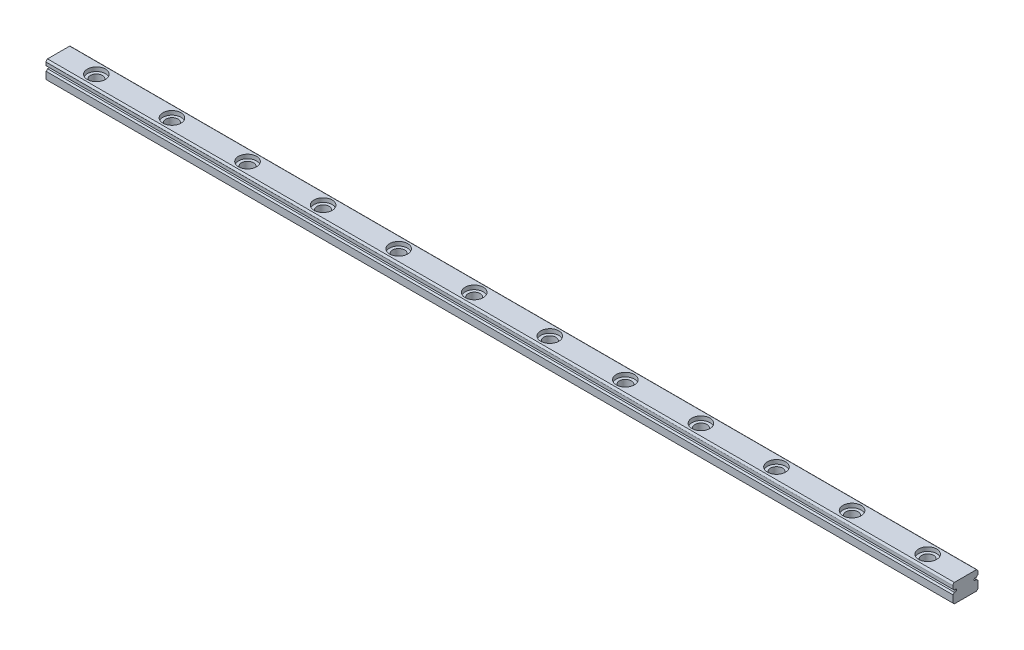
SolidWorks part; units mm, degrees
ref_plane "Front Plane" through (0, 0, 0) normal (0, 0, 1) x (1, 0, 0)
ref_plane "Top Plane" through (0, 0, 0) normal (0, 1, 0) x (1, 0, 0)
ref_plane "Right Plane" through (0, 0, 0) normal (1, 0, 0) x (0, 0, -1)
sketch "Sketch1" plane through (0, 0, 0) normal (1, 0, 0) x (0, 0, -1)
  line L0 (-2.5, 0.3) -> (-2.2, 0)
  line L1 (-2.2, 0) -> (2.2, 0)
  line L2 (2.2, 0) -> (2.5, 0.3)
  line L3 (2.5, 0.3) -> (2.5, 1.723)
  line L4 (2.1917, 2) -> (1.85, 2)
  line L5 (1.75, 2.1) -> (1.75, 2.3)
  line L6 (1.85, 2.4) -> (2.1917, 2.4)
  line L7 (2.5, 2.677) -> (2.5, 3.3)
  line L8 (2.2, 3.7) -> (-2.2, 3.7)
  line L9 (-2.5, 3.3) -> (-2.5, 2.677)
  line L10 (-2.1917, 2.4) -> (-1.85, 2.4)
  line L11 (-1.75, 2.3) -> (-1.75, 2.1)
  line L12 (-1.85, 2) -> (-2.1917, 2)
  line L13 (-2.5, 1.723) -> (-2.5, 0.3)
  arc A0 (2.5, 1.723) -> (2.1917, 2) centre (2.65, 2.2) cw
  arc A1 (1.85, 2) -> (1.75, 2.1) centre (1.85, 2.1) cw
  arc A2 (1.75, 2.3) -> (1.85, 2.4) centre (1.85, 2.3) cw
  arc A3 (2.1917, 2.4) -> (2.5, 2.677) centre (2.65, 2.2) cw
  arc A4 (2.5, 3.3) -> (2.2, 3.7) centre (1.9137, 3.1727) ccw
  arc A5 (-2.2, 3.7) -> (-2.5, 3.3) centre (-1.9137, 3.1727) ccw
  arc A6 (-2.5, 2.677) -> (-2.1917, 2.4) centre (-2.65, 2.2) cw
  arc A7 (-1.85, 2.4) -> (-1.75, 2.3) centre (-1.85, 2.3) cw
  arc A8 (-1.75, 2.1) -> (-1.85, 2) centre (-1.85, 2.1) cw
  arc A9 (-2.1917, 2) -> (-2.5, 1.723) centre (-2.65, 2.2) cw
extrude "Extrude1" add sketch "Sketch1" along normal blind 180
sketch "Sketch2" plane through (0, 0, 0) normal (0, 0, -1) x (-1, 0, 0)
  line L0 (-7.5, 3.7) -> (-5.7, 3.7)
  line L1 (-5.7, 3.7) -> (-5.7, 2.9)
  line L2 (-5.7, 2.9) -> (-6.3, 2.9)
  line L3 (-6.3, 2.9) -> (-6.3, 0.2)
  line L4 (-6.3, 0.2) -> (-6.1, 0)
  line L5 (-6.1, 0) -> (-7.5, 0)
  line L6 (0, 1.723) -> (0, 0.3) construction
  line L7 (-7.5, 0) -> (-7.5, 3.7) construction
  line L8 (-7.5, 3.7) -> (-7.5, 0)
  line L9 (-180, 0) -> (0, 0) construction
  line L10 (-180, 3.7) -> (0, 3.7) construction
  dimension "D1" = 7.5
  dimension "D2" = 2.4
  dimension "D3" = 2.8
  dimension "D4" = 45
  dimension "D5" = 3.6
  dimension "D6" = 0.8
revolve "Cut-Revolve1" cut sketch "Sketch2" angle 360 about L7 reverse direction yes
sketch "Sketch3" plane through (45, 0, 0) normal (0, 0, -1) x (-1, 0, 0)
  line L0 (-127.5, 3.7) -> (-125.7, 3.7)
  line L1 (-125.7, 3.7) -> (-125.7, 2.9)
  line L2 (-125.7, 2.9) -> (-126.3, 2.9)
  line L3 (-126.3, 2.9) -> (-126.3, 0.2)
  line L4 (-126.3, 0.2) -> (-126.1, 0)
  line L5 (-126.1, 0) -> (-127.5, 0)
  line L6 (-135, 1.723) -> (-135, 0.3) construction
  line L7 (-127.5, 0) -> (-127.5, 3.7) construction
  line L8 (-135, 3.7) -> (45, 3.7) construction
  line L9 (-135, 0) -> (45, 0) construction
  line L10 (-127.5, 3.7) -> (-127.5, 0)
  dimension "D1" = 7.5
  dimension "D2" = 2.4
  dimension "D3" = 2.8
  dimension "D4" = 3.6
  dimension "D5" = 0.8
  dimension "D6" = 45
revolve "Cut-Revolve2" cut sketch "Sketch3" angle 360 about L7 reverse direction yes
ref_axis "Axis1" through (-3, 0, 0) along (1, 0, 0)
pattern_linear "LPattern1" count 11 spacing 15 along (-1, 0, 0) of "Cut-Revolve2"
